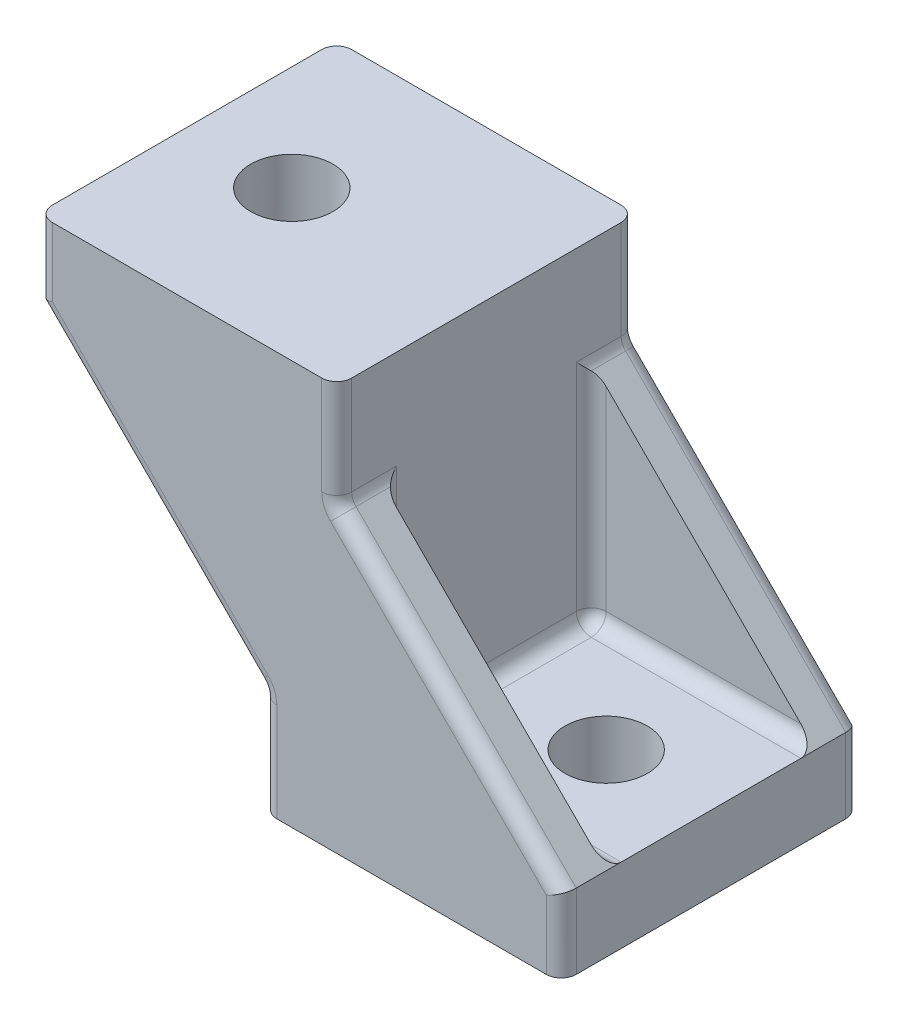
SolidWorks part; units mm, degrees
ref_plane "Front Plane" through (0, 0, 0) normal (0, 0, 1) x (1, 0, 0)
ref_plane "Top Plane" through (0, 0, 0) normal (0, 1, 0) x (1, 0, 0)
ref_plane "Right Plane" through (0, 0, 0) normal (1, 0, 0) x (0, 0, -1)
sketch "Sketch1" plane through (0, 0, 0) normal (0, 0, 1) x (1, 0, 0)
  line L0 (0, 0) -> (0, 22)
  line L1 (0, 22) -> (-15, 22)
  line L2 (-15, 22) -> (-15, 27)
  line L3 (-15, 27) -> (5, 27)
  line L4 (5, 27) -> (5, 5)
  line L5 (5, 5) -> (20, 5)
  line L6 (20, 5) -> (20, 0)
  line L7 (20, 0) -> (0, 0)
  point P5 (0, 0)
  dimension "D1" = 5
  dimension "D2" = 5
  dimension "D3" = 20
  dimension "D4" = 5
  dimension "D5" = 15
  dimension "D6" = 27
extrude "Boss-Extrude1" add sketch "Sketch1" along normal mid plane 20
sketch "Sketch2" plane through (0, 27, 0) normal (0, 1, 0) x (1, 0, 0)
  line L0 (-15, -10) -> (-15, 10) construction
  circle A0 centre (-8, 0) radius 2.75
  point P4 (0, 0)
  dimension "D1" = 5.5
  dimension "D2" = 7
extrude "Cut-Extrude1" cut sketch "Sketch2" against normal through all
sketch "Sketch3" plane through (0, 5, 0) normal (0, 1, 0) x (1, 0, 0)
  line L0 (20, -10) -> (20, 10) construction
  circle A0 centre (13, 0) radius 2.75
  point P4 (0, 0)
  dimension "D1" = 5.5
  dimension "D2" = 7
extrude "Cut-Extrude2" cut sketch "Sketch3" against normal through all
sketch "Sketch5" plane through (0, 0, -10) normal (0, 0, -1) x (-1, 0, 0)
  line L0 (-20, 5) -> (-5, 20)
  line L1 (-5, 5) -> (-5, 27) construction
  line L2 (-20, 5) -> (-5, 5) construction
  dimension "D1" = 45
rib "Rib7" sketch "Sketch5" sketch "Sketch5" thickness 3 extrusion direction parallel to sketch draft on no parameters "D1"=3
sketch "Sketch6" plane through (0, 0, -10) normal (0, 0, -1) x (-1, 0, 0)
  line L0 (15, 22) -> (0, 7)
  line L1 (15, 22) -> (0, 22) construction
  line L2 (0, 22) -> (0, 0) construction
  point P5 (0, 0)
  dimension "D1" = 135
rib "Rib8" sketch "Sketch6" sketch "Sketch6" thickness 3 extrusion direction parallel to sketch draft on no parameters "D1"=3
mirror "Mirror1" about plane through (0, 0, 0) normal (0, 0, 1) of "Rib8", "Rib7"
fillet "Fillet1" radius 1 14 edges at (0, 7, 8.5) (0, 7, -8.5) (5, 20, -8.5) (5, 20, 8.5) (5, 12.5, -7) (12.5, 5, -7) (12.5, 5, 7) (5, 12.5, 7) (5, 5, 0) (0, 22, 0) (0, 14.5, -7) (0, 14.5, 7) (-7.5, 22, 7) (-7.5, 22, -7)
fillet "Fillet2" radius 1 16 edges at (-7.6464, 14.6464, -10) (-0.0761, 6.9685, -10) (-7.6464, 14.6464, 10) (-0.0761, 6.9685, 10) (12.6464, 12.3536, 10) (5.0761, 20.0315, 10) (12.6464, 12.3536, -10) (5.0761, 20.0315, -10) (0, 3.2929, -10) (0, 3.2929, 10) (5, 23.7071, 10) (5, 23.7071, -10) (20, 2.5, -10) (20, 2.5, 10) (-15, 24.5, 10) (-15, 24.5, -10)
